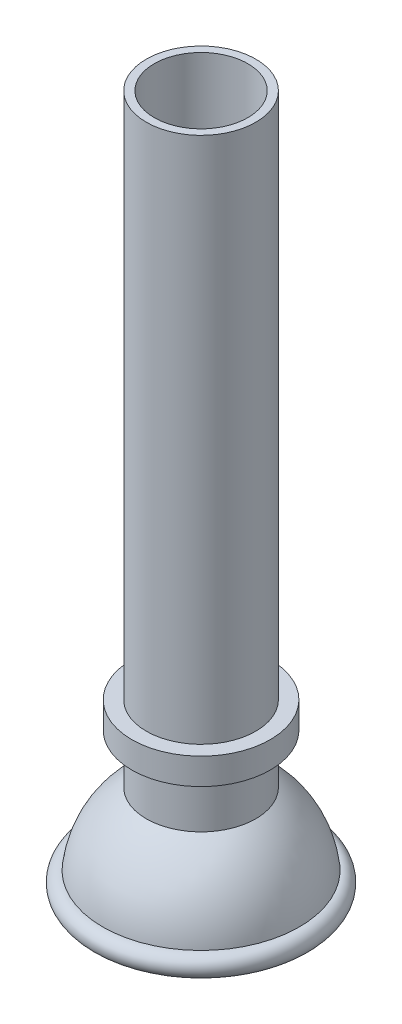
SolidWorks part; units mm, degrees
ref_plane "Front Plane" through (0, 0, 0) normal (1, 0, 0) x (0, 1, 0)
ref_plane "Top Plane" through (0, 0, 0) normal (0, 0, 1) x (0, 1, 0)
ref_plane "Right Plane" through (0, 0, 0) normal (0, 1, 0) x (-1, 0, 0)
sketch "Sketch1" plane through (0, 0, 0) normal (1, 0, 0) x (0, 1, 0)
  line L0 (0, 0) -> (-132.08, 0) construction
  line L1 (0, 0) -> (0, 10.541) construction
  line L2 (0, 10.541) -> (-101.6, 10.541)
  line L3 (-101.6, 10.541) -> (-101.6, 13.335)
  line L4 (-101.6, 13.335) -> (-106.68, 13.335)
  line L5 (-106.68, 13.335) -> (-106.68, 10.541)
  line L6 (-106.68, 10.541) -> (-116.2121, 10.541)
  line L7 (-132.08, 19.05) -> (-132.08, 0) construction
  line L8 (0, 10.541) -> (0, 9.017)
  line L9 (0, 9.017) -> (-106.68, 9.017)
  line L10 (-106.68, 9.017) -> (-106.68, 6.35)
  line L11 (-106.68, 6.35) -> (-116.2911, 6.35)
  arc A0 (-116.2121, 10.541) -> (-130.0509, 18.9416) centre (-132.08, 0) ccw
  circle A1 centre (-132.08, 19.05) radius 2.032
  arc A2 (-132.08, 17.018) -> (-116.2911, 6.35) centre (-132.08, 0) cw
  point P19 (0, 0)
  point P21 (-139.2876, -9.8612)
  point P22 (0, 0)
  dimension "D7" = 4.064
  dimension "D8" = 19.05
  dimension "D1" = 21.082
  dimension "D2" = 132.08
  dimension "D3" = 25.4
  dimension "D4" = 5.08
  dimension "D5" = 26.67
  dimension "D6" = 38.1
  dimension "D9" = 18.034
  dimension "D10" = 12.7
revolve "Revolve1" add sketch "Sketch1" angle 360 about L0 region at (0, -75.3088, 10.3542) region at (0, -132.08, 19.05)
